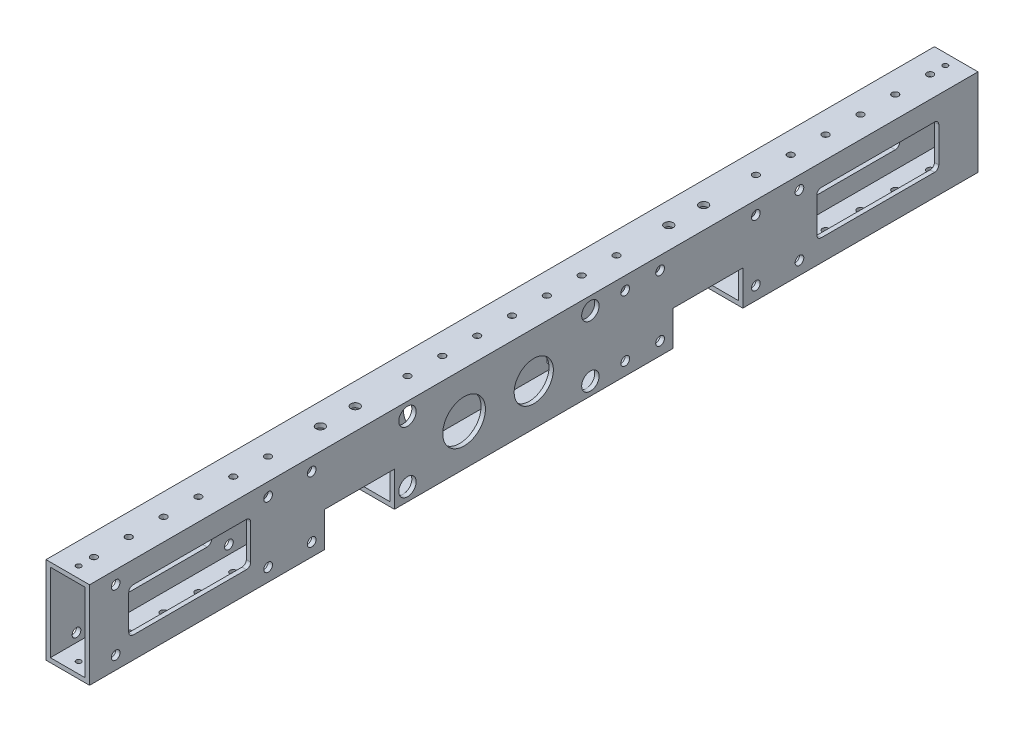
SolidWorks part; units mm, degrees
ref_plane "Front Plane" through (0, 0, 0) normal (0, 0, 1) x (1, 0, 0)
ref_plane "Top Plane" through (0, 0, 0) normal (0, 1, 0) x (1, 0, 0)
ref_plane "Right Plane" through (0, 0, 0) normal (1, 0, 0) x (0, 0, -1)
sketch "Sketch1" plane through (0, 0, 0) normal (0, 0, 1) x (1, 0, 0)
  line L1 (-12.1647, 2.5103) -> (19.5853, 2.5103)
  line L2 (-12.1647, 2.5103) -> (-12.1647, -60.9897)
  line L3 (-12.1647, -60.9897) -> (19.5853, -60.9897)
  line L4 (19.5853, 2.5103) -> (19.5853, -60.9897)
  line L5 (-8.9897, -0.6647) -> (16.4103, -0.6647)
  line L6 (-8.9897, -0.6647) -> (-8.9897, -57.8147)
  line L7 (-8.9897, -57.8147) -> (16.4103, -57.8147)
  line L8 (16.4103, -0.6647) -> (16.4103, -57.8147)
  dimension "D1" = 63.5
  dimension "D2" = 31.75
  dimension "D3" = 3.175
  dimension "D4" = 3.175
  dimension "D5" = 3.175
  dimension "D6" = 3.175
extrude "Boss-Extrude1" add sketch "Sketch1" along normal blind 647.7
sketch "Sketch3" plane through (-12.1647, 0, 0) normal (-1, 0, 0) x (0, 0, 1)
  line L0 (0, 2.5103) -> (0, -60.9897) construction
  line L1 (31.75, -13.3647) -> (114.3, -13.3647)
  line L2 (28.575, -16.5397) -> (28.575, -41.9397)
  line L3 (31.75, -45.1147) -> (114.3, -45.1147)
  line L4 (117.475, -16.5397) -> (117.475, -41.9397)
  line L5 (647.7, 2.5103) -> (0, 2.5103) construction
  line L6 (647.7, -60.9897) -> (0, -60.9897) construction
  line L7 (323.85, 2.5103) -> (323.85, -60.9897) construction
  line L8 (530.225, -16.5397) -> (530.225, -41.9397)
  line L9 (615.95, -45.1147) -> (533.4, -45.1147)
  line L10 (619.125, -16.5397) -> (619.125, -41.9397)
  line L11 (615.95, -13.3647) -> (533.4, -13.3647)
  line L12 (647.7, 2.5103) -> (647.7, -60.9897) construction
  line L13 (171.45, -60.9897) -> (222.25, -60.9897)
  line L14 (171.45, -60.9897) -> (171.45, -35.5897)
  line L15 (171.45, -35.5897) -> (222.25, -35.5897)
  line L16 (222.25, -60.9897) -> (222.25, -35.5897)
  line L17 (425.45, -60.9897) -> (476.25, -60.9897)
  line L18 (476.25, -60.9897) -> (476.25, -35.5897)
  line L19 (476.25, -35.5897) -> (425.45, -35.5897)
  line L20 (425.45, -60.9897) -> (425.45, -35.5897)
  arc A0 (28.575, -41.9397) -> (31.75, -45.1147) centre (31.75, -41.9397) ccw
  arc A1 (114.3, -45.1147) -> (117.475, -41.9397) centre (114.3, -41.9397) ccw
  arc A2 (114.3, -13.3647) -> (117.475, -16.5397) centre (114.3, -16.5397) cw
  arc A3 (31.75, -13.3647) -> (28.575, -16.5397) centre (31.75, -16.5397) ccw
  arc A4 (615.95, -13.3647) -> (619.125, -16.5397) centre (615.95, -16.5397) cw
  arc A5 (533.4, -13.3647) -> (530.225, -16.5397) centre (533.4, -16.5397) ccw
  arc A6 (533.4, -45.1147) -> (530.225, -41.9397) centre (533.4, -41.9397) cw
  arc A7 (619.125, -41.9397) -> (615.95, -45.1147) centre (615.95, -41.9397) cw
  line M7 (0, -60.9897) -> (647.7, -60.9897)
  dimension "D5" = 3.175
  dimension "D1" = 28.575
  dimension "D2" = 15.875
  dimension "D3" = 31.75
  dimension "D4" = 88.9
  dimension "D6" = 25.4
  dimension "D7" = 50.8
  dimension "D8" = 171.45
  dimension "D9" = 50.8
  dimension "D10" = 25.4
  dimension "D11" = 171.45
extrude "Cut-Extrude1" cut sketch "Sketch3" against normal up to surface (31.75 mm away) contours L1 A3 L2 A0 L3 A1 L4 A2 | A7 L10 A4 L11 A5 L8 A6 L9 | L16 L15 L14 M7 | L20 L18 L19 M7 region at (-12.1647, -29.2397, 73.025) region at (-12.1647, -29.2397, 574.675) region at (-12.1647, -48.2897, 196.85) region at (-12.1647, -48.2897, 450.85) up to face at (19.5853, -29.2397, 323.85)
sketch "Sketch6" plane through (19.5853, 0, 0) normal (1, 0, 0) x (0, 0, -1)
  line L1 (-425.45, -60.9897) -> (-222.25, -60.9897) construction
  line L2 (-415.925, -7.0147) -> (-282.575, -7.0147) construction
  line L3 (-415.925, -7.0147) -> (-415.925, -51.4647) construction
  line L4 (-647.7, -60.9897) -> (-647.7, 2.5103) construction
  line L5 (-415.925, -51.4647) -> (-282.575, -51.4647) construction
  line L6 (-282.575, -7.0147) -> (-282.575, -51.4647) construction
  circle A0 centre (-323.85, -30.8272) radius 14.2875
  circle A1 centre (-374.65, -30.8272) radius 15.5575
  circle A2 centre (-415.925, -7.0147) radius 3.175
  circle A3 centre (-282.575, -7.0147) radius 3.175
  circle A4 centre (-415.925, -51.4647) radius 3.175
  circle A5 centre (-282.575, -51.4647) radius 3.175
  dimension "D1" = 28.575
  dimension "D4" = 50.8
  dimension "D6" = 20.6375
  dimension "D8" = 92.075
  dimension "D7" = 6.35
  dimension "D10" = 31.115
  dimension "D2" = 30.1625
  dimension "D3" = 323.85
  dimension "D5" = 23.8125
  dimension "D9" = 41.275
extrude "Cut-Extrude2" cut sketch "Sketch6" against normal up to surface (31.75 mm away) up to face at (-12.1647, -41.9397, 323.85)
sketch "Sketch7" plane through (19.5853, 0, 0) normal (1, 0, 0) x (0, 0, -1)
  circle A0 centre (-415.925, -7.0147) radius 6.35
  circle A1 centre (-415.925, -51.4647) radius 6.35
  circle A2 centre (-282.575, -51.4647) radius 6.35
  circle A3 centre (-282.575, -7.0147) radius 6.35
  dimension "D1" = 12.7
extrude "Cut-Extrude3" cut sketch "Sketch7" against normal up to next
sketch "Sketch8" plane through (0, 2.5103, 0) normal (0, 1, 0) x (1, 0, 0)
  line L0 (3.7103, -171.45) -> (3.7103, -476.25) construction
  line L1 (-12.1647, -171.45) -> (19.5853, -171.45) construction
  line L2 (-12.1647, -171.45) -> (-12.1647, -222.25) construction
  line L3 (-12.1647, -222.25) -> (19.5853, -222.25) construction
  line L4 (19.5853, -171.45) -> (19.5853, -222.25) construction
  line L5 (19.5853, -425.45) -> (-12.1647, -425.45) construction
  line L6 (19.5853, -425.45) -> (19.5853, -476.25) construction
  line L7 (19.5853, -476.25) -> (-12.1647, -476.25) construction
  line L8 (-12.1647, -425.45) -> (-12.1647, -476.25) construction
  circle A0 centre (3.7103, -184.15) radius 3.175
  circle A1 centre (3.7103, -209.55) radius 3.175
  circle A2 centre (3.7103, -438.15) radius 3.175
  circle A3 centre (3.7103, -463.55) radius 3.175
  dimension "D5" = 6.35
  dimension "D6" = 12.7
  dimension "D7" = 25.4
  dimension "D8" = 12.7
  dimension "D9" = 25.4
  dimension "D1" = 50.8
  dimension "D2" = 31.75
  dimension "D3" = 50.8
  dimension "D4" = 31.75
extrude "Cut-Extrude4" cut sketch "Sketch8" against normal through all
sketch "Sketch9" plane through (0, 2.5103, 0) normal (0, 1, 0) x (1, 0, 0)
  line L0 (19.5853, 0) -> (-12.1647, 0) construction
  line L1 (-12.1647, -647.7) -> (-12.1647, 0) construction
  line L2 (19.5853, -647.7) -> (-12.1647, -647.7) construction
  circle A0 centre (3.7103, -639.7625) radius 1.8415
  circle A1 centre (3.7103, -7.9375) radius 1.8415
  dimension "D1" = 3.683
  dimension "D4" = 3.683
  dimension "D2" = 7.9375
  dimension "D3" = 15.875
  dimension "D5" = 7.9375
  dimension "D6" = 15.875
extrude "Cut-Extrude5" cut sketch "Sketch9" against normal up to surface (63.5 mm away) up to face at (3.7103, -60.9897, 561.975)
sketch "Sketch10" plane through (19.5853, 0, 0) normal (1, 0, 0) x (0, 0, -1)
  line L0 (-647.7, 2.5103) -> (0, 2.5103) construction
  line L1 (-171.45, -60.9897) -> (-120.65, -60.9897) construction
  line L2 (-171.45, -60.9897) -> (-171.45, 2.5103) construction
  line L3 (-171.45, 2.5103) -> (-120.65, 2.5103) construction
  line L4 (-120.65, -60.9897) -> (-120.65, 2.5103) construction
  line L5 (-161.925, -51.4647) -> (-130.175, -51.4647) construction
  line L6 (-130.175, -51.4647) -> (-130.175, -7.0147) construction
  line L7 (-161.925, -7.0147) -> (-130.175, -7.0147) construction
  line L8 (-161.925, -51.4647) -> (-161.925, -7.0147) construction
  line L9 (-231.775, -51.4647) -> (-257.175, -51.4647) construction
  line L10 (-222.25, -60.9897) -> (-266.7, -60.9897) construction
  line L11 (-222.25, -60.9897) -> (-222.25, 2.5103) construction
  line L12 (-222.25, 2.5103) -> (-266.7, 2.5103) construction
  line L13 (-266.7, -60.9897) -> (-266.7, 2.5103) construction
  line L14 (-257.175, -51.4647) -> (-257.175, -7.0147) construction
  line L15 (-231.775, -7.0147) -> (-257.175, -7.0147) construction
  line L16 (-231.775, -51.4647) -> (-231.775, -7.0147) construction
  line L17 (-485.775, -7.0147) -> (-517.525, -7.0147) construction
  line L18 (-476.25, -60.9897) -> (-527.05, -60.9897) construction
  line L19 (-476.25, -60.9897) -> (-476.25, 2.5103) construction
  line L20 (-476.25, 2.5103) -> (-527.05, 2.5103) construction
  line L21 (-527.05, -60.9897) -> (-527.05, 2.5103) construction
  line L22 (-517.525, -51.4647) -> (-517.525, -7.0147) construction
  line L23 (-485.775, -51.4647) -> (-517.525, -51.4647) construction
  line L24 (-485.775, -51.4647) -> (-485.775, -7.0147) construction
  line L25 (-628.65, -7.0147) -> (-628.65, -51.4647) construction
  line L26 (-647.7, -60.9897) -> (-647.7, 2.5103) construction
  circle A0 centre (-628.65, -7.0147) radius 3.175
  circle A1 centre (-517.525, -7.0147) radius 3.175
  circle A2 centre (-485.775, -7.0147) radius 3.175
  circle A3 centre (-517.525, -51.4647) radius 3.175
  circle A4 centre (-485.775, -51.4647) radius 3.175
  circle A5 centre (-628.65, -51.4647) radius 3.175
  circle A6 centre (-257.175, -7.0147) radius 3.175
  circle A7 centre (-231.775, -7.0147) radius 3.175
  circle A8 centre (-257.175, -51.4647) radius 3.175
  circle A9 centre (-231.775, -51.4647) radius 3.175
  circle A10 centre (-161.925, -7.0147) radius 3.175
  circle A11 centre (-130.175, -7.0147) radius 3.175
  circle A12 centre (-161.925, -51.4647) radius 3.175
  circle A13 centre (-130.175, -51.4647) radius 3.175
  dimension "D7" = 6.35
  dimension "D1" = 50.8
  dimension "D3" = 44.45
  dimension "D6" = 19.05
  dimension "D2" = 9.525
  dimension "D4" = 9.525
  dimension "D5" = 9.525
extrude "Cut-Extrude6" cut sketch "Sketch10" against normal through all
sketch "Sketch11" plane through (0, -60.9897, 0) normal (0, -1, 0) x (1, 0, 0)
  line L0 (19.5853, 647.7) -> (19.5853, 476.25) construction
  line L1 (-12.1647, 647.7) -> (19.5853, 647.7) construction
  circle A0 centre (3.7103, 628.65) radius 2.3813
  circle A1 centre (3.7103, 603.25) radius 2.3813
  circle A2 centre (3.7103, 577.85) radius 2.3813
  circle A3 centre (3.7103, 552.45) radius 2.3813
  circle A4 centre (3.7103, 527.05) radius 2.3813
  circle A5 centre (3.7103, 501.65) radius 2.3813
  circle A9 centre (3.7103, 400.05) radius 2.3813
  circle A10 centre (3.7103, 374.65) radius 2.3813
  circle A11 centre (3.7103, 349.25) radius 2.3813
  circle A12 centre (3.7103, 323.85) radius 2.3813
  circle A13 centre (3.7103, 298.45) radius 2.3813
  circle A14 centre (3.7103, 273.05) radius 2.3813
  circle A15 centre (3.7103, 247.65) radius 2.3813
  circle A19 centre (3.7103, 146.05) radius 2.3813
  circle A20 centre (3.7103, 120.65) radius 2.3813
  circle A21 centre (3.7103, 95.25) radius 2.3813
  circle A22 centre (3.7103, 69.85) radius 2.3813
  circle A23 centre (3.7103, 44.45) radius 2.3813
  circle A24 centre (3.7103, 19.05) radius 2.3813
  circle A25 centre (3.7103, 476.25) radius 2.3813 [skipped]
  circle A26 centre (3.7103, 450.85) radius 2.3813 [skipped]
  circle A27 centre (3.7103, 425.45) radius 2.3813 [skipped]
  circle A28 centre (3.7103, 222.25) radius 2.3813 [skipped]
  circle A29 centre (3.7103, 196.85) radius 2.3813 [skipped]
  circle A30 centre (3.7103, 171.45) radius 2.3813 [skipped]
  dimension "D1" = 4.7625
  dimension "D2" = 15.875
  dimension "D3" = 19.05
  dimension "D4" = 25
extrude "Cut-Extrude7" cut sketch "Sketch11" against normal through all
